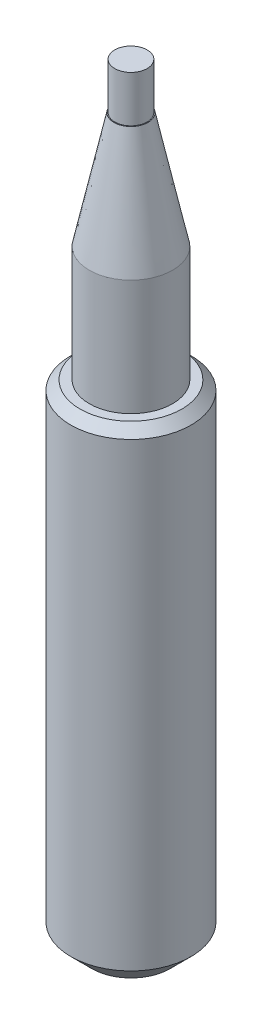
SolidWorks part; units mm, degrees
ref_plane "Front Plane" through (0, 0, 0) normal (0, 0, 1) x (1, 0, 0)
ref_plane "Top Plane" through (0, 0, 0) normal (0, 1, 0) x (1, 0, 0)
ref_plane "Right Plane" through (0, 0, 0) normal (1, 0, 0) x (0, 0, -1)
sketch "Sketch1" plane through (0, 0, 0) normal (0, 1, 0) x (1, 0, 0)
  circle A0 centre (0, 0) radius 9
  circle A1 centre (0, 0) radius 13
  dimension "D1" = 18
  dimension "D2" = 4
extrude "Boss-Extrude1" add sketch "Sketch1" along normal blind 50 contours A0 region at (0, 0, 0)
extrude "Boss-Extrude2" add sketch "Sketch1<3>" against normal blind 106 contours A1 A0 | A0 region at (0, 0, 0) region at (-12.6323, 0, 0)
sketch "Sketch1<3>" plane through (0, 0, 0) normal (0, 1, 0) x (1, 0, 0) same geometry as "Sketch1"
sketch "Sketch2" plane through (0, 50, 0) normal (0, 1, 0) x (1, 0, 0)
  circle A0 centre (0, 0) radius 3.5
  dimension "D1" = 7
extrude "Boss-Extrude3" add sketch "Sketch2" along normal blind 10
chamfer "Chamfer1" distance 4.5 angle 45 1 edges at (0, -106, 13)
chamfer "Chamfer2" distance 25 angle 12 1 edges at (0, 50, 9) first distance on face at (0, 50, 9)
sketch "Sketch3" plane through (0, -106, 0) normal (0, -1, 0) x (1, 0, 0)
  circle A0 centre (0, 10) radius 1
  circle A1 centre (10, 0) radius 1
  circle A2 centre (0, -10) radius 1
  circle A3 centre (-10, 0) radius 1
  point P12 (0, 0)
  dimension "D2" = 2
  dimension "D1" = 10
  dimension "D3" = 4
extrude "Cut-Extrude1" cut sketch "Sketch3" against normal blind 10
chamfer "Chamfer3" distance 2 angle 45 1 edges at (0, 0, 13)
